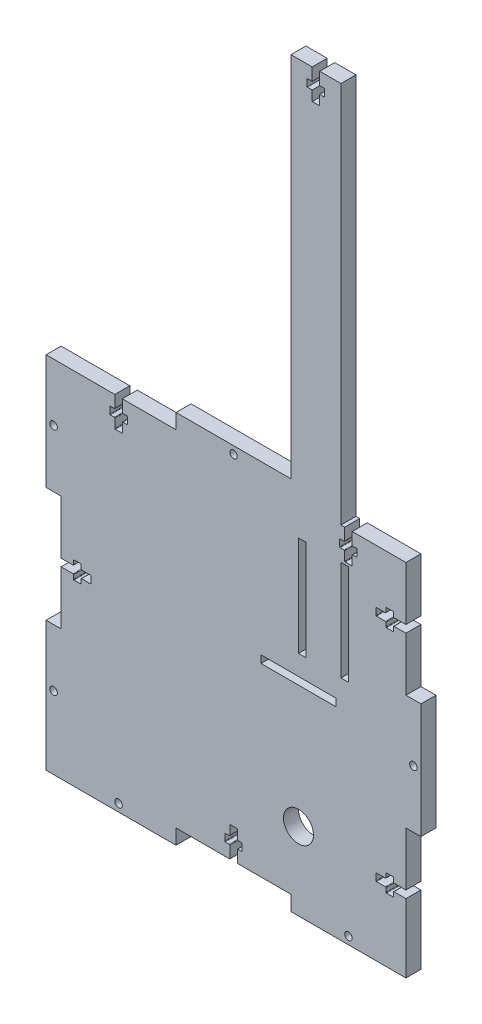
SolidWorks part; units mm, degrees
ref_plane "Front Plane" through (0, 0, 0) normal (0, 0, 1) x (1, 0, 0)
ref_plane "Top Plane" through (0, 0, 0) normal (0, 1, 0) x (1, 0, 0)
ref_plane "Right Plane" through (0, 0, 0) normal (1, 0, 0) x (0, 0, -1)
sketch "Sketch1" plane through (0, 0, 0) normal (0, 0, 1) x (1, 0, 0)
  line L0 (-69, 69) -> (-23, 69)
  line L5 (-75, -75) -> (75, -75) construction
  line L6 (-75, -75) -> (-75, 75) construction
  line L7 (-75, 75) -> (75, 75) construction
  line L8 (75, -75) -> (75, 75) construction
  line L9 (75, 23) -> (69, 23)
  line L10 (69, -23) -> (75, -23)
  line L11 (-69, -69) -> (69, -69) construction
  line L12 (-69, -69) -> (-69, 69) construction
  line L13 (-69, 69) -> (69, 69) construction
  line L14 (69, -69) -> (69, 69) construction
  line L15 (-69, -69) -> (69, 69) construction
  line L16 (69, -69) -> (69, -23)
  line L17 (-23, 69) -> (-23, 75)
  line L18 (-23, 75) -> (23, 75)
  line L19 (23, 75) -> (23, 69)
  line L20 (23, 69) -> (69, 69)
  line L21 (75, -23) -> (75, 23)
  line L22 (69, 23) -> (69, 69)
  line L23 (-75, 23) -> (-69, 23)
  line L24 (-69, 69) -> (-75, 69)
  line L25 (-75, 69) -> (-75, 23)
  line L26 (69, -69) -> (69, -75)
  line L27 (69, -75) -> (23, -75)
  line L28 (23, -75) -> (23, -69)
  line L29 (23, -69) -> (-23, -69)
  line L30 (-23, -69) -> (-23, -75)
  line L31 (-23, -75) -> (-69, -75)
  line L32 (-69, -75) -> (-69, -69) construction
  line L33 (-69, 23) -> (-69, -23)
  line L34 (-69, -23) -> (-75, -23)
  line L35 (-75, -23) -> (-75, -69)
  line L36 (-75, -69) -> (-69, -69) construction
  line L37 (-46, 69) -> (-46, -75) construction
  line L38 (-69, 69) -> (69, -69) construction
  line L39 (-75, -75) -> (-69, -75)
  line L40 (-75, -75) -> (-75, -69)
  point P0 (0, 0)
  point P6 (-7, -7)
  point P26 (0, -75)
  point P27 (-75, 0)
  dimension "D1" = 150
  dimension "D2" = 150
  dimension "D5" = 46
  dimension "D3" = 6
  dimension "D6" = 6
  dimension "D7" = 6
extrude "Box Side" add sketch "Sketch1" along normal blind 6
sketch "Sketch2" plane through (0, 0, 6) normal (0, 0, 1) x (1, 0, 0)
  line L0 (23, 72) -> (-23, 72) construction
  line L1 (23, 75) -> (23, 69) construction
  line L2 (-23, 69) -> (-23, 75) construction
  line L3 (-46, 69) -> (-46, -75) construction
  line L5 (0, 75) -> (0, 69) construction
  line L6 (-23, 75) -> (23, 75) construction
  line L7 (-69, 69) -> (69, 69) construction
  line L16 (-46, 69) -> (-46, -75) construction
  line L21 (0, -69) -> (0, 69) construction
  line L35 (-69, 69) -> (-23, 69) construction
  line L36 (-44.5, 69) -> (-44.5, 64.2)
  line L37 (-44.3, 64) -> (-42.7, 64)
  line L38 (-42.5, 63.8) -> (-42.5, 61.2)
  line L39 (-42.7, 61) -> (-44.3, 61)
  line L40 (-44.5, 60.8) -> (-44.5, 57.2)
  line L46 (-44.7, 57) -> (-47.3, 57)
  line L48 (-44.5, 69) -> (-47.5, 69)
  line L51 (-47.5, 60.8) -> (-47.5, 57.2)
  line L52 (-49.3, 61) -> (-47.7, 61)
  line L53 (-49.5, 63.8) -> (-49.5, 61.2)
  line L54 (-47.7, 64) -> (-49.3, 64)
  line L55 (-47.5, 69) -> (-47.5, 64.2)
  line L56 (47.5, 69) -> (47.5, 64.2)
  line L57 (47.7, 64) -> (49.3, 64)
  line L58 (49.5, 63.8) -> (49.5, 61.2)
  line L59 (49.3, 61) -> (47.7, 61)
  line L60 (47.5, 60.8) -> (47.5, 57.2)
  line L61 (44.5, 69) -> (47.5, 69)
  line L62 (44.7, 57) -> (47.3, 57)
  line L63 (44.5, 60.8) -> (44.5, 57.2)
  line L64 (42.7, 61) -> (44.3, 61)
  line L65 (42.5, 63.8) -> (42.5, 61.2)
  line L66 (44.3, 64) -> (42.7, 64)
  line L67 (44.5, 69) -> (44.5, 64.2)
  line L68 (-69, -69) -> (69, 69) construction
  line L69 (-69, -69) -> (69, 69) construction
  line L70 (75, 0) -> (69, 0) construction
  line L71 (72, 23) -> (72, -23) construction
  line L72 (69, 44.5) -> (64.2, 44.5)
  line L73 (64, 44.3) -> (64, 42.7)
  line L74 (63.8, 42.5) -> (61.2, 42.5)
  line L75 (61, 42.7) -> (61, 44.3)
  line L76 (60.8, 44.5) -> (57.2, 44.5)
  line L77 (57, 44.7) -> (57, 47.3)
  line L78 (69, 44.5) -> (69, 47.5)
  line L79 (60.8, 47.5) -> (57.2, 47.5)
  line L80 (61, 49.3) -> (61, 47.7)
  line L81 (63.8, 49.5) -> (61.2, 49.5)
  line L82 (64, 47.7) -> (64, 49.3)
  line L83 (69, 47.5) -> (64.2, 47.5)
  line L84 (69, -47.5) -> (64.2, -47.5)
  line L85 (64, -47.7) -> (64, -49.3)
  line L86 (63.8, -49.5) -> (61.2, -49.5)
  line L87 (61, -49.3) -> (61, -47.7)
  line L88 (60.8, -47.5) -> (57.2, -47.5)
  line L89 (69, -44.5) -> (69, -47.5)
  line L90 (57, -44.7) -> (57, -47.3)
  line L91 (60.8, -44.5) -> (57.2, -44.5)
  line L92 (61, -42.7) -> (61, -44.3)
  line L93 (63.8, -42.5) -> (61.2, -42.5)
  line L94 (64, -44.3) -> (64, -42.7)
  line L95 (69, -44.5) -> (64.2, -44.5)
  line L120 (-69, 69) -> (69, -69) construction
  line L121 (-69, 69) -> (69, -69) construction
  line L122 (-1.5, -69) -> (1.5, -69)
  line L123 (-23, -69) -> (23, -69) construction
  line L124 (1.5, -69) -> (1.5, -64.2)
  line L125 (1.7, -64) -> (3.3, -64)
  line L126 (3.5, -63.8) -> (3.5, -61.2)
  line L127 (3.3, -61) -> (1.7, -61)
  line L128 (1.5, -60.8) -> (1.5, -57.2)
  line L129 (1.3, -57) -> (-1.3, -57)
  line L130 (-1.5, -60.8) -> (-1.5, -57.2)
  line L131 (-3.3, -61) -> (-1.7, -61)
  line L132 (-3.5, -63.8) -> (-3.5, -61.2)
  line L133 (-1.7, -64) -> (-3.3, -64)
  line L134 (-1.5, -69) -> (-1.5, -64.2)
  line L135 (-69, -1.5) -> (-64.2, -1.5)
  line L136 (-64, -1.7) -> (-64, -3.3)
  line L137 (-63.8, -3.5) -> (-61.2, -3.5)
  line L138 (-61, -3.3) -> (-61, -1.7)
  line L139 (-60.8, -1.5) -> (-57.2, -1.5)
  line L140 (-57, 1.3) -> (-57, -1.3)
  line L141 (-60.8, 1.5) -> (-57.2, 1.5)
  line L142 (-61, 3.3) -> (-61, 1.7)
  line L143 (-63.8, 3.5) -> (-61.2, 3.5)
  line L144 (-64, 1.7) -> (-64, 3.3)
  line L145 (-69, 1.5) -> (-64.2, 1.5)
  line L146 (-69, -1.5) -> (-69, 1.5)
  line L147 (-69, -72) -> (-23, -72) construction
  line L148 (-23, 69) -> (-75, 69) construction
  line L149 (-23, -75) -> (-23, -69) construction
  line L150 (-69, -69) -> (-69, -75) construction
  line L151 (-75, -75) -> (-23, -75) construction
  circle A0 centre (0, 72) radius 1.5
  arc A1 (-44.5, 57.2) -> (-44.7, 57) centre (-44.7, 57.2) cw
  arc A2 (-44.3, 61) -> (-44.5, 60.8) centre (-44.3, 60.8) ccw
  arc A3 (-42.5, 61.2) -> (-42.7, 61) centre (-42.7, 61.2) cw
  arc A4 (-42.7, 64) -> (-42.5, 63.8) centre (-42.7, 63.8) cw
  arc A5 (-44.5, 64.2) -> (-44.3, 64) centre (-44.3, 64.2) ccw
  arc A6 (-47.5, 64.2) -> (-47.7, 64) centre (-47.7, 64.2) cw
  arc A7 (-49.3, 64) -> (-49.5, 63.8) centre (-49.3, 63.8) ccw
  arc A8 (-49.5, 61.2) -> (-49.3, 61) centre (-49.3, 61.2) ccw
  arc A9 (-47.7, 61) -> (-47.5, 60.8) centre (-47.7, 60.8) cw
  arc A10 (-47.5, 57.2) -> (-47.3, 57) centre (-47.3, 57.2) ccw
  arc A11 (47.5, 57.2) -> (47.3, 57) centre (47.3, 57.2) cw
  arc A12 (47.7, 61) -> (47.5, 60.8) centre (47.7, 60.8) ccw
  arc A13 (49.5, 61.2) -> (49.3, 61) centre (49.3, 61.2) cw
  arc A14 (49.3, 64) -> (49.5, 63.8) centre (49.3, 63.8) cw
  arc A15 (47.5, 64.2) -> (47.7, 64) centre (47.7, 64.2) ccw
  arc A16 (44.5, 64.2) -> (44.3, 64) centre (44.3, 64.2) cw
  arc A17 (42.7, 64) -> (42.5, 63.8) centre (42.7, 63.8) ccw
  arc A18 (42.5, 61.2) -> (42.7, 61) centre (42.7, 61.2) ccw
  arc A19 (44.3, 61) -> (44.5, 60.8) centre (44.3, 60.8) cw
  arc A20 (44.5, 57.2) -> (44.7, 57) centre (44.7, 57.2) ccw
  arc A21 (57.2, 44.5) -> (57, 44.7) centre (57.2, 44.7) cw
  arc A22 (61, 44.3) -> (60.8, 44.5) centre (60.8, 44.3) ccw
  arc A23 (61.2, 42.5) -> (61, 42.7) centre (61.2, 42.7) cw
  arc A24 (64, 42.7) -> (63.8, 42.5) centre (63.8, 42.7) cw
  arc A25 (64.2, 44.5) -> (64, 44.3) centre (64.2, 44.3) ccw
  arc A26 (64.2, 47.5) -> (64, 47.7) centre (64.2, 47.7) cw
  arc A27 (64, 49.3) -> (63.8, 49.5) centre (63.8, 49.3) ccw
  arc A28 (61.2, 49.5) -> (61, 49.3) centre (61.2, 49.3) ccw
  arc A29 (61, 47.7) -> (60.8, 47.5) centre (60.8, 47.7) cw
  arc A30 (57.2, 47.5) -> (57, 47.3) centre (57.2, 47.3) ccw
  arc A31 (57.2, -47.5) -> (57, -47.3) centre (57.2, -47.3) cw
  arc A32 (61, -47.7) -> (60.8, -47.5) centre (60.8, -47.7) ccw
  arc A33 (61.2, -49.5) -> (61, -49.3) centre (61.2, -49.3) cw
  arc A34 (64, -49.3) -> (63.8, -49.5) centre (63.8, -49.3) cw
  arc A35 (64.2, -47.5) -> (64, -47.7) centre (64.2, -47.7) ccw
  arc A36 (64.2, -44.5) -> (64, -44.3) centre (64.2, -44.3) cw
  arc A37 (64, -42.7) -> (63.8, -42.5) centre (63.8, -42.7) ccw
  arc A38 (61.2, -42.5) -> (61, -42.7) centre (61.2, -42.7) ccw
  arc A39 (61, -44.3) -> (60.8, -44.5) centre (60.8, -44.3) cw
  arc A40 (57.2, -44.5) -> (57, -44.7) centre (57.2, -44.7) ccw
  circle A41 centre (72, 0) radius 1.5
  arc A62 (1.5, -57.2) -> (1.3, -57) centre (1.3, -57.2) ccw
  arc A63 (1.7, -61) -> (1.5, -60.8) centre (1.7, -60.8) cw
  arc A64 (3.5, -61.2) -> (3.3, -61) centre (3.3, -61.2) ccw
  arc A65 (3.3, -64) -> (3.5, -63.8) centre (3.3, -63.8) ccw
  arc A66 (1.5, -64.2) -> (1.7, -64) centre (1.7, -64.2) cw
  arc A67 (-1.5, -64.2) -> (-1.7, -64) centre (-1.7, -64.2) ccw
  arc A68 (-3.3, -64) -> (-3.5, -63.8) centre (-3.3, -63.8) cw
  arc A69 (-3.5, -61.2) -> (-3.3, -61) centre (-3.3, -61.2) cw
  arc A70 (-1.7, -61) -> (-1.5, -60.8) centre (-1.7, -60.8) ccw
  arc A71 (-1.5, -57.2) -> (-1.3, -57) centre (-1.3, -57.2) cw
  arc A72 (-57.2, -1.5) -> (-57, -1.3) centre (-57.2, -1.3) ccw
  arc A73 (-61, -1.7) -> (-60.8, -1.5) centre (-60.8, -1.7) cw
  arc A74 (-61.2, -3.5) -> (-61, -3.3) centre (-61.2, -3.3) ccw
  arc A75 (-64, -3.3) -> (-63.8, -3.5) centre (-63.8, -3.3) ccw
  arc A76 (-64.2, -1.5) -> (-64, -1.7) centre (-64.2, -1.7) cw
  arc A77 (-64.2, 1.5) -> (-64, 1.7) centre (-64.2, 1.7) ccw
  arc A78 (-64, 3.3) -> (-63.8, 3.5) centre (-63.8, 3.3) cw
  arc A79 (-61.2, 3.5) -> (-61, 3.3) centre (-61.2, 3.3) cw
  arc A80 (-61, 1.7) -> (-60.8, 1.5) centre (-60.8, 1.7) ccw
  arc A81 (-57.2, 1.5) -> (-57, 1.3) centre (-57.2, 1.3) cw
  circle A82 centre (-46, -72) radius 1.5
  circle A83 centre (46, -72) radius 1.5
  circle A84 centre (-72, 46) radius 1.5
  circle A85 centre (-72, -46) radius 1.5
  point P6 (0, 72)
  point P38 (0, 0)
  point P56 (-46, 57)
  point P88 (46, 57)
  point P161 (57, 46)
  point P162 (57, -46)
  point P198 (0, -57)
  point P231 (-57, 0)
  point P234 (-42.5, 62.5)
  dimension "D1" = 3
  dimension "D2" = 0.2
  dimension "D8" = 0.2
  dimension "D14" = 3
  dimension "D4" = 3
  dimension "D7" = 1.5
  dimension "D10" = 3
  dimension "D12" = 1.5
  dimension "D9" = 12
  dimension "D11" = 5
  dimension "D13" = 7
  dimension "D3" = 12
  dimension "D5" = 7
  dimension "D6" = 5
extrude "Screw Cut-outs" cut sketch "Sketch2" against normal through all
sketch "Bearing Hole" plane through (0, 0, 6) normal (0, 0, 1) x (1, 0, 0)
  line L0 (20, -69) -> (50020, -69) construction
  line L1 (69, -44.5) -> (69, -23) construction
  line L4 (26, -41) -> (50026, -41) construction
  line L5 (26.5774, -47) -> (50026.5774, -47) construction
  line L8 (29, -52) -> (29, -50052) construction
  circle A0 centre (26, -44) radius 3 construction
  circle A1 centre (26, -54) radius 15 construction
  circle A2 centre (26, -44) radius 6
  dimension "D2" = 6
  dimension "D4" = 30
  dimension "D5" = 12
  dimension "D1" = 7
  dimension "D3" = 43
extrude "Shaft Hole" cut sketch "Bearing Hole" against normal through all
sketch "Sketch4" plane through (0, 0, 0) normal (0, 0, -1) x (-1, 0, 0)
  line L0 (-72, 1.5) -> (49928, 1.5) construction
  line L1 (-41, 8) -> (-11, 8)
  line L2 (-41, 8) -> (-41, 5)
  line L3 (-41, 5) -> (-11, 5)
  line L4 (-11, 8) -> (-11, 5)
  line L5 (-75, -23) -> (-75, 23) construction
  line L6 (-69, 23) -> (-69, 44.5) construction
  line L7 (-46, 56) -> (-43, 56)
  line L8 (-46, 56) -> (-46, 16)
  line L9 (-46, 16) -> (-43, 16)
  line L10 (-43, 56) -> (-43, 16)
  line L11 (-29, 56) -> (-26, 56)
  line L12 (-29, 56) -> (-29, 16)
  line L13 (-29, 16) -> (-26, 16)
  line L14 (-26, 56) -> (-26, 16)
  line L15 (-44.5, 69) -> (-23, 69) construction
  circle A1 centre (-72, 0) radius 1.5 construction
  point P18 (-29, 36)
  dimension "D1" = 3.5
  dimension "D2" = 30
  dimension "D3" = 3
  dimension "D4" = 34
  dimension "D5" = 14
  dimension "D6" = 23
  dimension "D7" = 13
  dimension "D8" = 3
  dimension "D9" = 40
extrude "Grooves" cut sketch "Sketch4" against normal up to surface (6 mm away) up to face at (32, -44, 6)
sketch "Sketch5" plane through (0, 69, 0) normal (0, 1, 0) x (1, 0, 0)
  line L0 (69, 0) -> (47.5, 0) construction
  line L1 (23, -6) -> (43, -6)
  line L2 (23, -6) -> (23, 0)
  line L3 (23, 0) -> (43, 0)
  line L4 (43, -6) -> (43, 0)
  line L5 (75, -6) -> (75, 0) construction
  dimension "D1" = 32
extrude "Boss-Extrude1" add sketch "Sketch5" along normal blind 153
sketch "Sketch6" plane through (0, 0, 0) normal (0, 0, -1) x (-1, 0, 0)
  line L0 (-34.5, 222) -> (-34.5, 217)
  line L1 (-43, 222) -> (-23, 222) construction
  line L2 (-34.5, 217) -> (-36.5, 217)
  line L3 (-36.5, 217) -> (-36.5, 214)
  line L4 (-36.5, 214) -> (-34.5, 214)
  line L5 (-34.5, 214) -> (-34.5, 210)
  line L6 (-34.5, 210) -> (-31.5, 210)
  line L7 (-31.5, 210) -> (-31.5, 214)
  line L8 (-31.5, 214) -> (-29.5, 214)
  line L9 (-29.5, 214) -> (-29.5, 217)
  line L10 (-29.5, 217) -> (-31.5, 217)
  line L11 (-31.5, 217) -> (-31.5, 222)
  line L12 (-34.5, 222) -> (-31.5, 222)
  line L13 (-29.5, 214) -> (-36.5, 214)
  point P4 (-33, 210)
  point P15 (0, 0)
  point P16 (-33, 222)
  point P17 (-33, 214)
  point P18 (-33, 222)
  dimension "D1" = 3
  dimension "D2" = 7
  dimension "D3" = 5
  dimension "D4" = 12
  dimension "D5" = 3
extrude "Cut-Extrude1" cut sketch "Sketch6" against normal through all contours L13 L8 L9 L10 L11 L12 L0 L2 L3 L4 | L7 L13 L5 L6 region at (33, 217.1667, 0) region at (33, 212, 0)
equation "\"filletRadius\"=0.2"
equation "\"D8@Sketch2\"=\"filletRadius\""
equation "\"D2@Sketch2\"=\"filletRadius\""
equation "\"fingerWidth\"= 46"
equation "\"D5@Sketch1\"=\"fingerWidth\""
equation "\"wallThickness\"= 6"
equation "\"D3@Sketch1\" = \"wallThickness\""
equation "\"D6@Sketch1\" = \"wallThickness\""
equation "\"D7@Sketch1\" = \"wallThickness\""
equation "\"D1@Box Side\" = \"wallThickness\""
equation "\"M3\"= 3"
equation "\"D14@Sketch2\"=\"M3\""
equation "\"D1@Sketch2\"=\"M3\""
equation "\"D12@Sketch2\"=\"M3\"/2"
equation "\"nutThickness\"=3"
equation "\"D10@Sketch2\" = \"nutThickness\""
equation "\"boltLength\"= 12"
equation "\"D9@Sketch2\" = \"boltLength\""
equation "\"distanceToNut\"= 5"
equation "\"D11@Sketch2\" = \"distanceToNut\""
equation "\"D13@Sketch2\" = \"nutWidth\""
equation "\"D7@Sketch2\"=\"M3\"/2"
equation "\"D4@Sketch2\" = \"nutThickness\""
equation "\"D3@Sketch2\" = \"boltLength\""
equation "\"D5@Sketch2\" = \"nutWidth\""
equation "\"D6@Sketch2\" = \"distanceToNut\""
equation "\"sideLength\"=150"
equation "\"D1@Sketch1\"=\"sideLength\""
equation "\"D2@Sketch1\"=\"sideLength\""
equation "\"nutWidth\"=7"
equation "\"D1@Sketch6\"=\"M3\""
equation "\"D2@Sketch6\"=\"nutWidth\""
equation "\"D3@Sketch6\"=\"distanceToNut\""
equation "\"D4@Sketch6\"=\"boltLength\""
equation "\"D5@Sketch6\"=\"nutThickness\""
